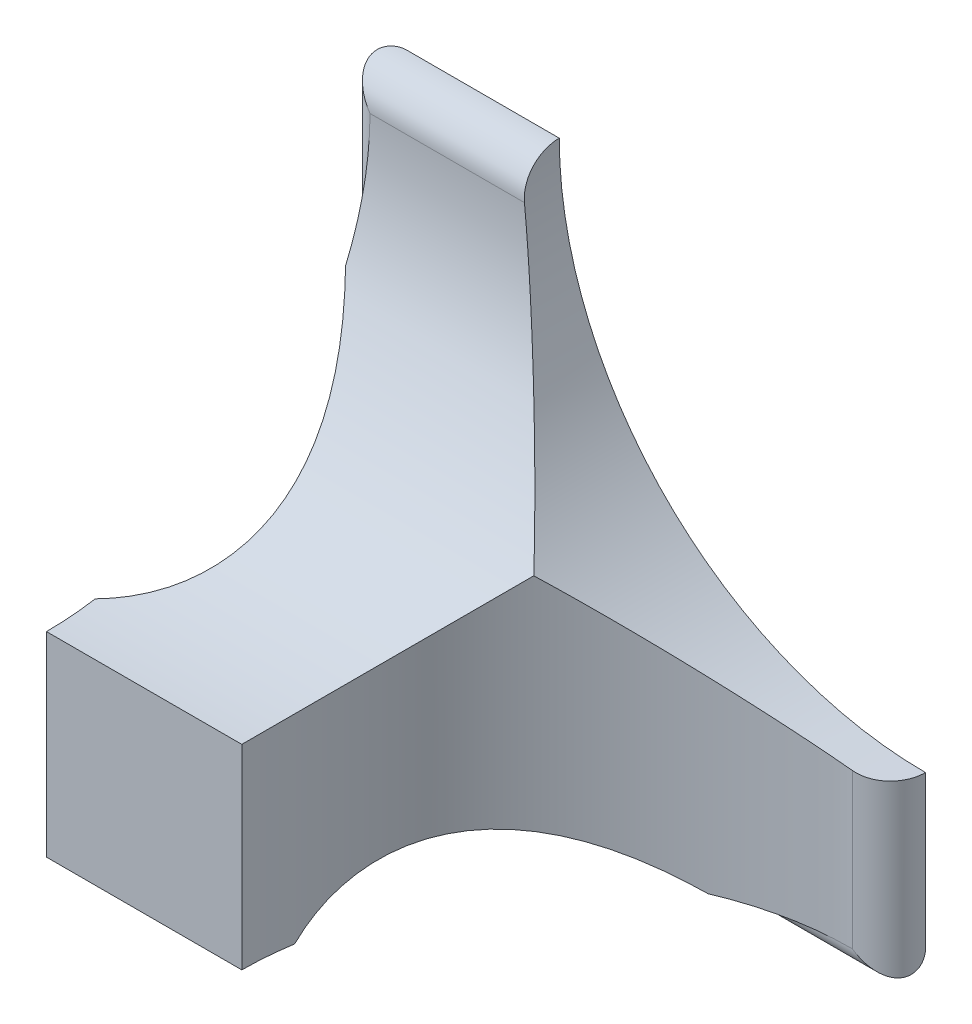
SolidWorks part; units mm, degrees
material "Золото без примесей"
ref_plane "Front" through (0, 0, 0) normal (0, 0, 1) x (1, 0, 0)
ref_plane "Top" through (0, 0, 0) normal (0, 1, 0) x (1, 0, 0)
ref_plane "Right" through (0, 0, 0) normal (1, 0, 0) x (0, 0, -1)
sketch "Эскиз1" plane through (0, 0, 0) normal (0, 0, 1) x (1, 0, 0)
  line L0 (0, 0) -> (22, 0)
  line L1 (22, 0) -> (22, 7)
  line L2 (0, 0) -> (19.7111, 19.7111) construction
  line L4 (11.3934, 11.3934) -> (0, 0)
  line L5 (22, 7) -> (22.8779, 7) construction
  line L6 (11.3934, 11.3934) -> (7.5702, 15.2166) construction
  arc A0 (22, 7) -> (11.3934, 11.3934) centre (22, 22) cw
  dimension "D1" = 45
  dimension "D2" = 7
  dimension "D3" = 22
extrude "Основная форма" add sketch "Эскиз1" along normal blind 14
sketch "Эскиз2" plane through (22, 0, 0) normal (1, 0, 0) x (0, 0, -1)
  line L1 (-14, -1) -> (0, -1)
  line L2 (0, 0.75) -> (0, -1)
  line L5 (-14, 0) -> (0, 0) construction
  line L6 (-14, 0) -> (-14, -1)
  line L8 (-14, 0) -> (-12, 0)
  line L10 (-1.5, 0.75) -> (-2.5, 0.75)
  line L11 (0, 0) -> (0, 7) construction
  line L12 (-10.4143, 2.5) -> (-4.9819, 2.5) construction
  arc A3 (-12, 0) -> (-2.5, 0.75) centre (-6.91, -3.9316) cw
  arc A4 (0, 0.75) -> (-1.5, 0.75) centre (-0.75, 0.75) cw
  dimension "D1" = 2.5
  dimension "D2" = 1
  dimension "D3" = 1.5
  dimension "D5" = 1
  dimension "D7" = 2
extrude "Вырез фигурный, фронт" cut sketch "Эскиз2" against normal through all
sketch "Эскиз3" plane through (0, 0, 0) normal (0, 1, 0) x (1, 0, 0)
  line L4 (22, 0) -> (22, -14)
  line L6 (22, -14) -> (8, -14)
  line L9 (0, -14) -> (22, -14) construction
  line L10 (0.75, -1.5) -> (22, -1.5) construction
  line L11 (20.5, -14) -> (20.5, -1.5) construction
  arc A4 (8, -14) -> (20.5, -1.5) centre (20.5, -14) cw
  arc A5 (20.5, -1.5) -> (22, 0) centre (20.5, 0) ccw
extrude "Вырез фигурный, бок" cut sketch "Эскиз3" along normal through all
sketch "Эскиз5" plane through (0, 0, 0) normal (0, 0, -1) x (-1, 0, 0)
  line L1 (-8.75, 4.75) -> (-4.75, 4.75) construction
  line L6 (-11.3934, 11.3934) -> (-0.75, 0.75) construction
  line L7 (-22, 0.75) -> (-0.75, 0.75) construction
  line L8 (-5.9216, 5.9216) -> (-2.2649, 9.5783) construction
  line L9 (-8, 8) -> (-11.3934, 11.3934) construction
  line L10 (-8.75, 4.75) -> (-12.75, 4.75)
  arc A0 (-5.9216, 5.9216) -> (-8.75, 4.75) centre (-8.75, 8.75) cw
  dimension "D2" = 4
  dimension "D1" = 4
  dimension "D3" = 8
extrude "Вырез под финсатор" cut sketch "Эскиз5" against normal blind 3 and the other way through all thin thin type mid plane wall 1.4
mirror "Зеркальное отражение1" about plane through (11.3934, 11.3934, 14) normal (0.7071, -0.7071, 0) of "Вырез под финсатор", "Вырез фигурный, фронт", "Вырез фигурный, бок", "Основная форма"
chamfer "Фаска1" distance 0.5 angle 45 8 edges at (12.75, 4.75, 0) (10.75, 5.45, 0) (6.4165, 6.4165, 0) (10.75, 4.05, 0) (5.4266, 5.4266, 0) (5.45, 10.75, 0) (4.05, 10.75, 0) (4.75, 12.75, 0)
